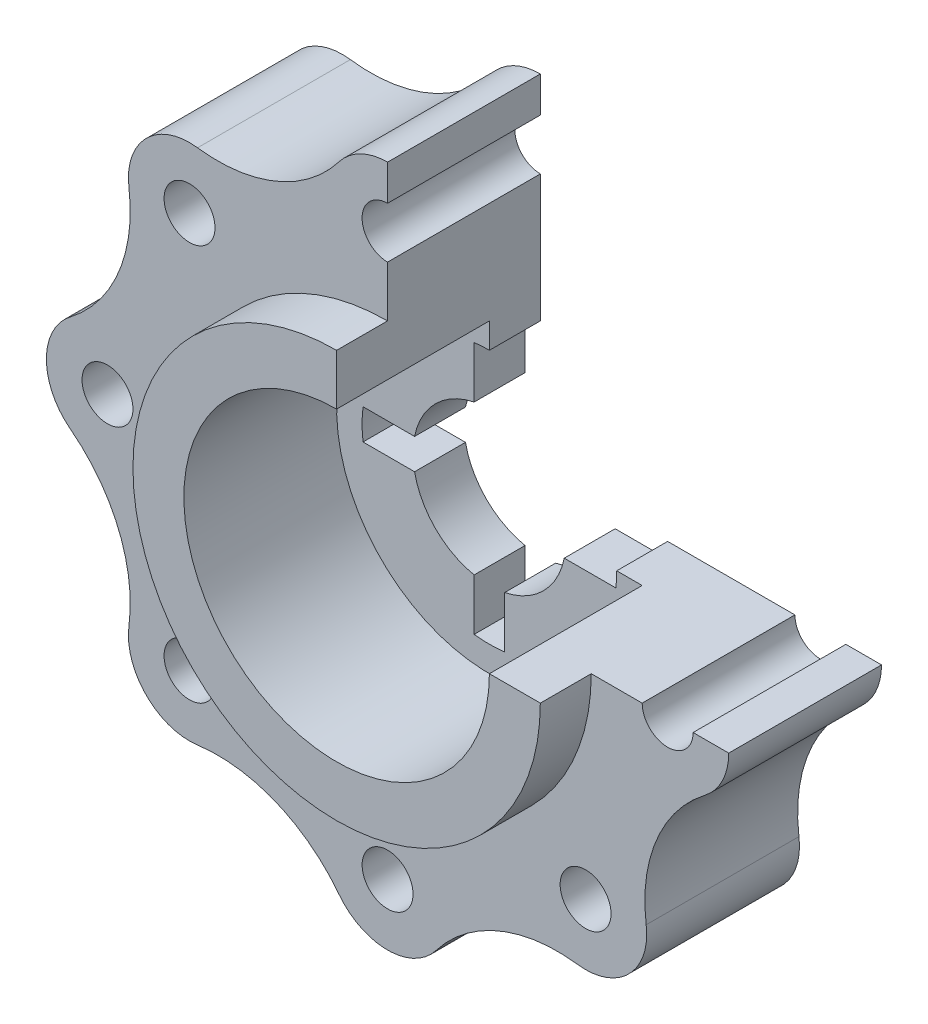
SolidWorks part; units mm, degrees
ref_plane "Front Plane" through (0, 0, 0) normal (0, 0, 1) x (1, 0, 0)
ref_plane "Top Plane" through (0, 0, 0) normal (0, 1, 0) x (1, 0, 0)
ref_plane "Right Plane" through (0, 0, 0) normal (1, 0, 0) x (0, 0, -1)
sketch "Sketch2" plane through (0, 0, 0) normal (0, 0, 1) x (1, 0, 0)
  line L0 (-24.8193, 3) -> (-14.6969, 3)
  line L1 (-24.8193, -3) -> (-14.6969, -3)
  line L2 (-3, -24.8193) -> (-3, -14.6969)
  line L3 (3, -24.8193) -> (3, -14.6969)
  line L4 (3, 24.8193) -> (3, 14.6969)
  line L5 (-3, 24.8193) -> (-3, 14.6969)
  line L6 (24.8193, -3) -> (14.6969, -3)
  line L7 (24.8193, 3) -> (14.6969, 3)
  circle A0 centre (0, 0) radius 55 construction
  circle A1 centre (0, 0) radius 40
  circle A2 centre (0, 0) radius 30
  arc A3 (-3, 14.6969) -> (-14.6969, 3) centre (0, 0) ccw
  arc A4 (-24.8193, 3) -> (-24.8193, -3) centre (0, 0) ccw
  arc A5 (3, 24.8193) -> (-3, 24.8193) centre (0, 0) ccw
  arc A6 (24.8193, -3) -> (24.8193, 3) centre (0, 0) ccw
  arc A7 (-3, -24.8193) -> (3, -24.8193) centre (0, 0) ccw
  arc A8 (14.6969, 3) -> (3, 14.6969) centre (0, 0) ccw
  arc A9 (3, -14.6969) -> (14.6969, -3) centre (0, 0) ccw
  arc A10 (-14.6969, -3) -> (-3, -14.6969) centre (0, 0) ccw
  arc A11 (-62.2927, 9.5298) -> (-62.2927, -9.5298) centre (-55, 0) ccw
  circle A12 centre (-55, 0) radius 5
  arc A13 (-37.309, 50.7862) -> (-50.7862, 37.309) centre (-38.8909, 38.8909) ccw
  circle A14 centre (-38.8909, 38.8909) radius 5
  arc A15 (9.5298, 62.2927) -> (-9.5298, 62.2927) centre (0, 55) ccw
  circle A16 centre (0, 55) radius 5
  arc A17 (50.7862, 37.309) -> (37.309, 50.7862) centre (38.8909, 38.8909) ccw
  circle A18 centre (38.8909, 38.8909) radius 5
  arc A19 (62.2927, -9.5298) -> (62.2927, 9.5298) centre (55, 0) ccw
  circle A20 centre (55, 0) radius 5
  arc A21 (37.309, -50.7862) -> (50.7862, -37.309) centre (38.8909, -38.8909) ccw
  circle A22 centre (38.8909, -38.8909) radius 5
  arc A23 (-9.5298, -62.2927) -> (9.5298, -62.2927) centre (0, -55) ccw
  circle A24 centre (0, -55) radius 5
  arc A25 (-50.7862, -37.309) -> (-37.309, -50.7862) centre (-38.8909, -38.8909) ccw
  circle A26 centre (-38.8909, -38.8909) radius 5
  arc A27 (-37.309, 50.7862) -> (-9.5298, 62.2927) centre (-33.3543, 80.5243) ccw
  arc A28 (9.5298, 62.2927) -> (37.309, 50.7862) centre (33.3543, 80.5243) ccw
  arc A29 (50.7862, 37.309) -> (62.2927, 9.5298) centre (80.5243, 33.3543) ccw
  arc A30 (62.2927, -9.5298) -> (50.7862, -37.309) centre (80.5243, -33.3543) ccw
  arc A31 (37.309, -50.7862) -> (9.5298, -62.2927) centre (33.3543, -80.5243) ccw
  arc A32 (-9.5298, -62.2927) -> (-37.309, -50.7862) centre (-33.3543, -80.5243) ccw
  arc A33 (-50.7862, -37.309) -> (-62.2927, -9.5298) centre (-80.5243, -33.3543) ccw
  arc A34 (-62.2927, 9.5298) -> (-50.7862, 37.309) centre (-80.5243, 33.3543) ccw
  point P9 (0, 0)
  point P27 (0, 0)
  point P30 (0, 0)
  point P55 (0, 0)
  point P71 (0, 0)
  dimension "D1" = 5
  dimension "D2" = 30
  dimension "D3" = 40
  dimension "D4" = 55
  dimension "D5" = 15
  dimension "D8" = 6
  dimension "D9" = 9.5298
  dimension "D10" = 37.309
  dimension "D11" = 50.7862
  dimension "D13" = 30
  dimension "D6" = 25
  dimension "D7" = 12
  dimension "D12" = 55
extrude "Boss-Extrude1" add sketch "Sketch2" along normal blind 30 contours A34 A11 A33 A25 A32 A23 A31 A21 A30 A19 A29 A17 A28 A15 A27 A13 A26 A24 A22 A20 A18 A16 A14 A12 A1 region at (-51.0572, 21.1486, 0)
extrude "Boss-Extrude2" add sketch "Sketch2<4>" along normal blind 40 contours A1 A2 region at (-38.8686, 0, 0)
sketch "Sketch2<4>" plane through (0, 0, 0) normal (0, 0, 1) x (1, 0, 0) same geometry as "Sketch2"
extrude "Boss-Extrude3" add sketch "Sketch2<5>" along normal blind 10 contours A2 A10 L1 A4 L0 A3 L5 A5 L4 A8 L7 A6 L6 A9 L3 A7 L2 region at (-29.1515, 0, 0)
sketch "Sketch2<5>" plane through (0, 0, 0) normal (0, 0, 1) x (1, 0, 0) same geometry as "Sketch2"
sketch "Sketch3" plane through (0, 0, 0) normal (0, 0, 1) x (1, 0, 0)
  line L0 (0, 0) -> (0, 75)
  line L1 (0, 0) -> (75, 0)
  line L2 (0, 75) -> (75, 75)
  line L3 (75, 75) -> (75, 0)
extrude "Cut-Extrude1" cut sketch "Sketch3" along normal blind 40
sketch "Sketch8" plane through (0, 0, 30) normal (0, 0, 1) x (1, 0, 0)
  circle A0 centre (0, 0) radius 55 construction
